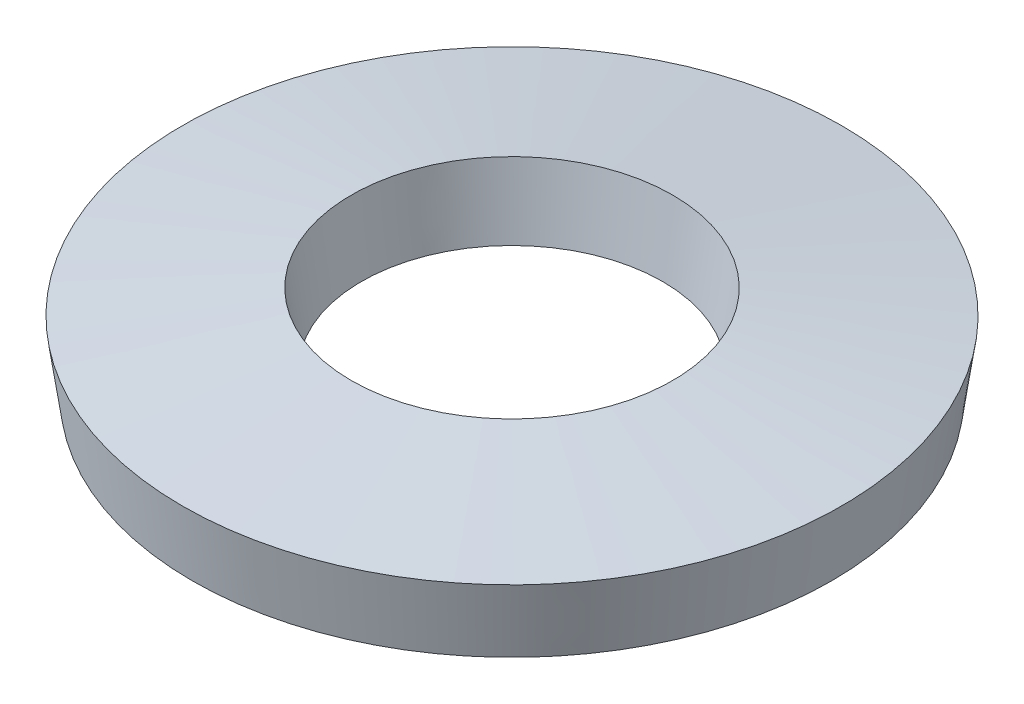
SolidWorks part; units mm, degrees
note: '?' marks a value the reader was unsure of.
ref_plane "Front" through (0, 0, 0) normal (0, 0, 1) x (1, 0, 0)
ref_plane "Top" through (0, 0, 0) normal (0, 1, 0) x (1, 0, 0)
ref_plane "Right" through (0, 0, 0) normal (1, 0, 0) x (0, 0, -1)
sketch "Sketch1" plane through (0, 0, 0) normal (0, 0, 1) x (1, 0, 0)
  line L0 (6.7867, 0) -> (3.2, 0.5152)
  line L1 (3.2, 0.5152) -> (3.4133, 2)
  line L2 (3.4133, 2) -> (7, 1.4848)
  line L3 (7, 1.4848) -> (6.7867, 0)
  line L4 (0, 0) -> (0, 2) construction
  line L5 (-7, 1.4848) -> (-6.7867, 0) construction
  line L6 (-3.4133, 2) -> (-7, 1.4848) construction
  line L7 (-3.2, 0.5152) -> (-3.4133, 2) construction
  line L8 (-6.7867, 0) -> (-3.2, 0.5152) construction
  point P5 (3.3066, 1.2576)
  point P8 (-3.3066, 1.2576)
  dimension "ID" = 6.4
  dimension "Thickness" = 1.5
  dimension "D1" = 3.6235
revolve "Revolve1" add sketch "Sketch1" angle 360 about L4
sketch "Sketch15" plane through (0, 0, 0) normal (0, 1, 0) x (1, 0, 0)
  circle A0 centre (0, 0) radius 7
  circle A1 centre (0, 0) radius 3.2
ref_plane "Plane10" through (0, 2, 0) normal (0, 1, 0) x (-1, 0, 0)
surface "Surface-Knit1"
surface "Surface-Extend1" parameters "D1"=1, "D2"=1
sketch "Sketch13" plane through (0, 2, 0) normal (0, 1, 0) x (-1, 0, 0)
  line L0 (-7.1701, 1.7518) -> (-2.8047, -0.2838)
  line L2 (-6.7867, 0) -> (-3.2, 0) construction
  circle A3 centre (0, 0) radius 2.819
  circle A4 centre (0, 0) radius 2.819 construction
  circle A6 centre (0, 0) radius 7.381
  circle A7 centre (0, 0) radius 7.381 construction
  dimension "D1" = 25
  dimension "D2" = 0.381
  dimension "D3" = 0.381
extrude "Cut-Extrude-Thin12" [suppressed] cut sketch "Sketch13" against normal offset from surface (0.3134 mm away) 0.1875 thin
surface "Surface-Knit2"
surface "Surface-Extend2" parameters "D1"=0.762, "D2"=0.762
sketch "Sketch14" plane through (0, 0, 0) normal (0, 1, 0) x (1, 0, 0)
  line L0 (7.1701, -1.7518) -> (2.8047, 0.2838) construction
  line L1 (7.1701, -1.7518) -> (2.8047, 0.2838)
extrude "Cut-Extrude-Thin13" [suppressed] cut sketch "Sketch14" along normal offset from surface (0.0096 mm away) 0.1875 thin
chamfer "Chamfer1" [suppressed] distance 0.1688 angle 45
pattern_circular "CirPattern3" [suppressed] count 24 over 360
delete or keep bodies "Body-Delete1" type delete bodies bodies 120
delete or keep bodies "Body-Delete2" type delete bodies bodies 119
ref_axis "Center Axis 1" through (0, 6.09, 0) along (0, -1, 0)?
equation "\"D1@Cut-Extrude-Thin12\" = \"Thickness@Sketch1\"*.125"
equation "\"D1@Cut-Extrude-Thin13\" = \"D1@Cut-Extrude-Thin12\""
equation "\"D1@Chamfer1\" = \"D1@Cut-Extrude-Thin12\"*.9"
